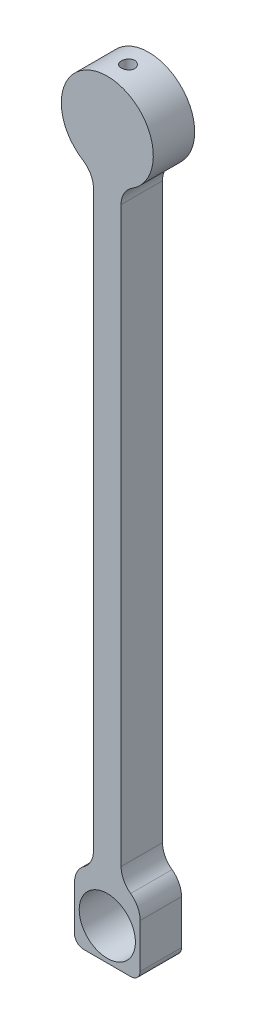
SolidWorks part; units mm, degrees
ref_plane "Front Plane" through (0, 0, 0) normal (0, 0, 1) x (1, 0, 0)
ref_plane "Top Plane" through (0, 0, 0) normal (0, 1, 0) x (1, 0, 0)
ref_plane "Right Plane" through (0, 0, 0) normal (1, 0, 0) x (0, 0, -1)
sketch "Sketch1" plane through (0, 0, 0) normal (0, 0, 1) x (1, 0, 0)
  line L5 (-1.8, 2.5239) -> (1.8, 2.5239)
  line L6 (-1.8629, 2.7239) -> (1.8629, 2.7239)
  circle A2 centre (0, 0) radius 10
  arc A4 (-1.8, 2.5239) -> (1.8, 2.5239) centre (0, 0) ccw
  arc A7 (-1.8629, 2.7239) -> (1.8629, 2.7239) centre (0, 0) ccw
  dimension "D1" = 0.2
  dimension "D4" = 20
  dimension "D2" = 6.2
  dimension "D3" = 3.6
extrude "Boss-Extrude1" add sketch "Sketch1" along normal blind 9 contours A2 region at (-9.7172, 0, 0)
sketch "Sketch2" plane through (0, 0, 0) normal (0, 0, -1) x (-1, 0, 0)
  line L5 (-10, -7) -> (10, -7)
  line L6 (-10, -7) -> (-10, -10)
  line L7 (-10, -10) -> (10, -10)
  line L8 (10, -7) -> (10, -10)
  circle A1 centre (0, 0) radius 10
  circle A2 centre (0, 0) radius 10
  circle M8 centre (0, 0) radius 10
  dimension "D2" = 3
  dimension "D1" = 0
extrude "Cut-Extrude1" cut sketch "Sketch2" against normal blind 10 contours L5 M8 region at (0, -8.2169, 0)
sketch "Sketch3" plane through (0, -7, 0) normal (0, -1, 0) x (1, 0, 0)
  line L4 (-7.1414, 0) -> (7.1414, 0)
  line L5 (7.1414, 0) -> (7.1414, 9)
  line L6 (7.1414, 9) -> (-7.1414, 9)
  line L7 (-7.1414, 9) -> (-7.1414, 0)
  line L8 (-7.1414, 0) -> (7.1414, 0)
  line L9 (7.1414, 0) -> (7.1414, 9)
  line L10 (7.1414, 9) -> (-7.1414, 9)
  line L11 (-7.1414, 9) -> (-7.1414, 0)
  dimension "D1" = 0
extrude "Boss-Extrude2" add sketch "Sketch3" along normal blind 150
sketch "Sketch4" plane through (0, 0, 0) normal (0, 0, -1) x (-1, 0, 0)
  line L0 (7.1414, -157) -> (-7.1414, -157) construction
  circle A0 centre (0, -150) radius 6.11
  dimension "D1" = 12.22
  dimension "D2" = 7
extrude "Cut-Extrude2" cut sketch "Sketch4" against normal blind 10 contours A0
fillet "Fillet1" radius 5 2 edges at (-7.1414, -7, 4.5) (7.1414, -7, 4.5)
fillet "Fillet2" radius 2 2 edges at (7.1414, -157, 4.5) (-7.1414, -157, 4.5)
sketch "Sketch5" [suppressed] plane through (0, 0, 10) normal (0, 0, 1) x (1, 0, 0)
  line L3 (-5.1414, -157) -> (5.1414, -157)
  line L4 (7.1414, -155) -> (7.1414, -8.8083)
  line L5 (-7.1414, -8.8083) -> (-7.1414, -155)
  line L6 (-5.1414, -157) -> (5.1414, -157)
  line L7 (7.1414, -155) -> (7.1414, -8.8083)
  line L8 (-7.1414, -8.8083) -> (-7.1414, -155)
  arc A5 (5.1414, -157) -> (7.1414, -155) centre (5.1414, -155) ccw
  arc A6 (8.0943, -5.8722) -> (7.1414, -8.8083) centre (12.1414, -8.8083) ccw
  arc A7 (8.0943, -5.8722) -> (-8.0943, -5.8722) centre (0, 0) ccw
  arc A8 (-7.1414, -8.8083) -> (-8.0943, -5.8722) centre (-12.1414, -8.8083) ccw
  arc A9 (-7.1414, -155) -> (-5.1414, -157) centre (-5.1414, -155) ccw
  arc A10 (5.1414, -157) -> (7.1414, -155) centre (5.1414, -155) ccw
  arc A11 (8.0943, -5.8722) -> (7.1414, -8.8083) centre (12.1414, -8.8083) ccw
  arc A12 (8.0943, -5.8722) -> (-8.0943, -5.8722) centre (0, 0) ccw
  arc A13 (-7.1414, -8.8083) -> (-8.0943, -5.8722) centre (-12.1414, -8.8083) ccw
  arc A14 (-7.1414, -155) -> (-5.1414, -157) centre (-5.1414, -155) ccw
  dimension "D1" = 0
extrude "Cut-Extrude3" [suppressed] cut sketch "Sketch5" against normal offset from surface (7 mm away) 3 up to face at (-6.11, -150, 0)
sketch "Sketch6" [suppressed] plane through (0, 0, 3) normal (0, 0, 1) x (1, 0, 0)
  line L0 (7.1414, -8.8083) -> (7.1414, -155) construction
  line L1 (-7.1414, -8.8083) -> (7.1414, -8.8083)
  line L2 (-7.1414, -8.8083) -> (-7.1414, -157)
  line L3 (-7.1414, -157) -> (7.1414, -157)
  line L4 (7.1414, -8.8083) -> (7.1414, -157)
  line L5 (0, -157) -> (0, -8.8083) construction
  line L6 (-7.1414, -82.9041) -> (7.1414, -82.9041) construction
  line L7 (5.1414, -157) -> (-5.1414, -157) construction
  point P660 (0, -82.9041)
extrude "Cut-Extrude4" [suppressed] cut sketch "Sketch6" against normal through all
sketch "Sketch8" plane through (0, 0, 0) normal (0, 0, -1) x (-1, 0, 0)
  line L0 (0, 0) -> (0, -150)
  line L1 (-3, -12.6886) -> (3, -12.6886) construction
  line L2 (-3, -12.6886) -> (-3, -137.3114)
  line L3 (-7.1414, -8.8083) -> (-7.1414, -155)
  line L4 (-5.1414, -157) -> (5.1414, -157)
  line L5 (7.1414, -155) -> (7.1414, -8.8083)
  line L6 (-7.1414, -8.8083) -> (-7.1414, -155)
  line L7 (-5.1414, -157) -> (5.1414, -157)
  line L8 (7.1414, -155) -> (7.1414, -8.8083)
  line L9 (-3, -137.3114) -> (3, -137.3114) construction
  line L10 (3, -12.6886) -> (3, -137.3114)
  line L11 (0, -137.3114) -> (0, -12.6886) construction
  line L12 (-3, -75) -> (3, -75) construction
  arc A0 (-8.0943, -5.8722) -> (-5.3333, -8.4591) centre (0, 0) ccw
  arc A1 (-5.3333, -141.5409) -> (-7.1414, -143) centre (0, -150) ccw
  arc A2 (-5.3333, -8.4591) -> (-3, -12.6886) centre (-8, -12.6886) cw
  arc A3 (-5.3333, -141.5409) -> (-3, -137.3114) centre (-8, -137.3114) ccw
  arc A4 (8.0943, -5.8722) -> (5.3333, -8.4591) centre (0, 0) cw
  arc A5 (-7.1414, -155) -> (-5.1414, -157) centre (-5.1414, -155) ccw
  arc A6 (5.1414, -157) -> (7.1414, -155) centre (5.1414, -155) ccw
  arc A7 (8.0943, -5.8722) -> (7.1414, -8.8083) centre (12.1414, -8.8083) ccw
  arc A8 (8.0943, -5.8722) -> (-8.0943, -5.8722) centre (0, 0) ccw
  arc A9 (-7.1414, -8.8083) -> (-8.0943, -5.8722) centre (-12.1414, -8.8083) ccw
  arc A10 (-7.1414, -155) -> (-5.1414, -157) centre (-5.1414, -155) ccw
  arc A11 (5.1414, -157) -> (7.1414, -155) centre (5.1414, -155) ccw
  arc A12 (8.0943, -5.8722) -> (7.1414, -8.8083) centre (12.1414, -8.8083) ccw
  arc A14 (-7.1414, -8.8083) -> (-8.0943, -5.8722) centre (-12.1414, -8.8083) ccw
  arc A15 (5.3333, -8.4591) -> (3, -12.6886) centre (8, -12.6886) ccw
  arc A16 (5.3333, -141.5409) -> (7.1414, -143) centre (0, -150) cw
  arc A17 (5.3333, -141.5409) -> (3, -137.3114) centre (8, -137.3114) cw
  point P193 (0, -75)
  line M20 (-7.1414, -8.8083) -> (-7.1414, -155)
  arc M25 (7.1414, -8.8083) -> (8.0943, -5.8722) centre (12.1414, -8.8083) cw
  arc M27 (-8.0943, -5.8722) -> (-7.1414, -8.8083) centre (-12.1414, -8.8083) cw
  dimension "D2" = 6
  dimension "D3" = 5
  dimension "D1" = 0
extrude "Cut-Extrude5" cut sketch "Sketch8" against normal through all and the other way through all contours A1 A3 L2 A2 A0 M27 M20 | A17 A16 L8 A4 A15 L10 M25 region at (5.0937, -74.9592, 0) region at (-5.0937, -74.9592, 0)
fillet "Fillet3" radius 5 2 edges
sketch "Sketch9" plane through (0, 0, 9) normal (0, 0, 1) x (1, 0, 0)
  line L0 (-1.8629, 2.7239) -> (1.8629, 2.7239) construction
  line L1 (-1.8629, 2.7239) -> (1.8629, 2.7239)
  arc A0 (-1.8629, 2.7239) -> (1.8629, 2.7239) centre (0, 0) ccw construction
  arc A1 (-1.8629, 2.7239) -> (1.8629, 2.7239) centre (0, 0) ccw
extrude "Boss-Extrude3" add sketch "Sketch9" against normal blind 2
ref_plane "Plane1" through (0, 10, 0) normal (0, 1, 0) x (1, 0, 0)
sketch "Sketch10" plane through (0, 10, 0) normal (0, 1, 0) x (1, 0, 0)
  circle A0 centre (0, -4.5) radius 1.45
  dimension "D1" = 2.9
  dimension "D2" = 4.5
extrude "Cut-Extrude6" cut sketch "Sketch10" against normal blind 10
